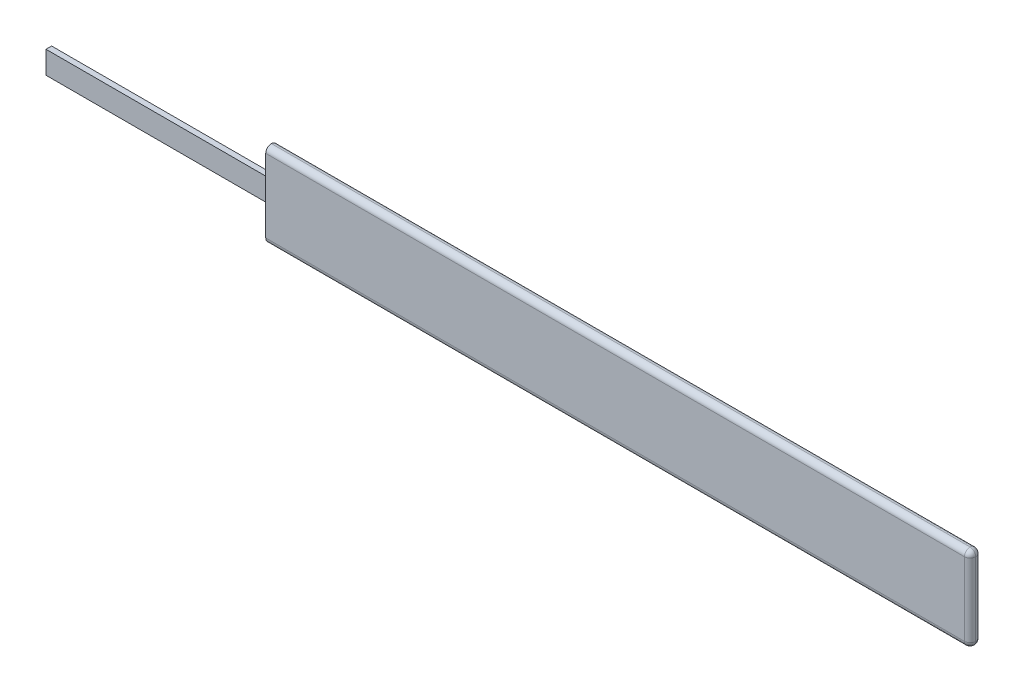
SolidWorks part; units mm, degrees
ref_plane "Plan de face" through (0, 0, 0) normal (0, 0, 1) x (1, 0, 0)
ref_plane "Plan de dessus" through (0, 0, 0) normal (0, 1, 0) x (1, 0, 0)
ref_plane "Plan de droite" through (0, 0, 0) normal (1, 0, 0) x (0, 0, -1)
sketch "Esquisse1" plane through (0, 0, 0) normal (0, 0, 1) x (1, 0, 0)
  line L0 (20, 2) -> (20, 7.5)
  line L1 (-20, 2) -> (20, 2)
  line L2 (-20, 2) -> (-20, -2)
  line L3 (-20, -2) -> (20, -2)
  line L4 (20, 2) -> (20, -2)
  line L5 (-20, 2) -> (20, -2) construction
  line L6 (-20, -2) -> (20, 2) construction
  line L7 (20, -2) -> (20, -7.5)
  line L9 (20, 7.5) -> (145, 7.5)
  line L10 (20, 7.5) -> (20, -7.5)
  line L11 (20, -7.5) -> (145, -7.5)
  line L12 (145, 7.5) -> (145, -7.5)
  point P0 (0, 0)
  dimension "D1" = 40
  dimension "D2" = 4
  dimension "D3" = 5.5
  dimension "D4" = 5.5
  dimension "D5" = 125
extrude "Boss.-Extru.2" add sketch "Esquisse1" along normal blind 2 contours L4 L1 L2 L3 | L12 L9 L0 L4 L7 L11 region at (0, 0, 0) region at (82.5, 0, 0)
sketch "Esquisse2" plane through (-20, 0, 0) normal (-1, 0, 0) x (0, 0, 1)
  line L0 (1, -2) -> (1, 2) construction
  line L1 (2, -2) -> (0, -2) construction
  line L2 (2, 2) -> (0, 2) construction
  line L4 (1, 2) -> (2, 2)
  line L5 (1, 2) -> (1, -2)
  line L6 (1, -2) -> (2, -2)
  line L7 (2, 2) -> (2, -2)
extrude "Enlèv. mat.-Extru.1" cut sketch "Esquisse2" against normal blind 40
fillet "Congé1" radius 1 4 edges at (82.5, -7.5, 0) (82.5, -7.5, 2) (82.5, 7.5, 2) (82.5, 7.5, 0)
fillet "Congé2" radius 1 6 edges at (145, 7.2071, 1.7071) (145, 7.2071, 0.2929) (145, -7.2071, 0.2929) (145, -7.2071, 1.7071) (145, 0, 0) (145, 0, 2)
